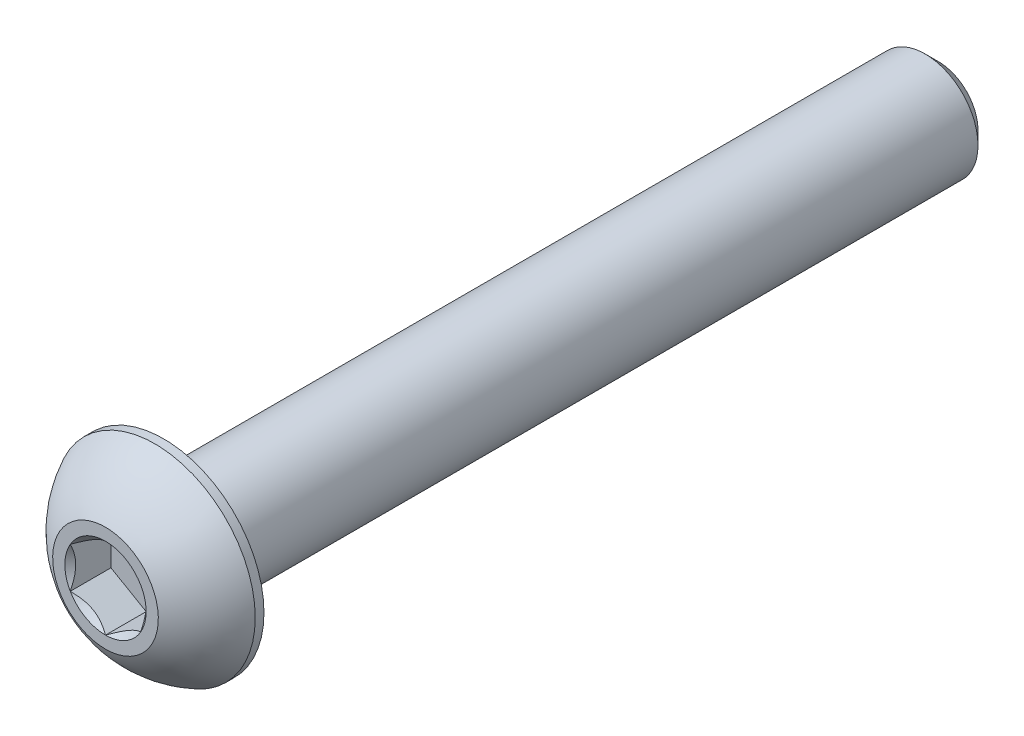
SolidWorks part; units mm, degrees
ref_plane "Front" through (0, 0, 0) normal (0, 0, 1) x (1, 0, 0)
ref_plane "Top" through (0, 0, 0) normal (0, 1, 0) x (1, 0, 0)
ref_plane "Right" through (0, 0, 0) normal (1, 0, 0) x (0, 0, -1)
sketch "Sketch1" plane through (0, 0, 0) normal (1, 0, 0) x (0, 0, -1)
  line L2 (1.65, 1.5) -> (23.65, 1.5)
  line L3 (23.65, 1.5) -> (23.65, 0)
  line L4 (23.65, 0) -> (1.65, 0)
  line L6 (1.4025, 2.85) -> (1.65, 2.85) construction
  line L7 (23.65, 1.5) -> (23.65, -1.5) construction
  line L8 (0, 0) -> (1.65, 0) construction
  line L9 (1.65, 2.85) -> (1.65, -2.85) construction
  line L11 (1.65, 1.5) -> (1.65, 0)
  line L13 (0, 1) -> (0, -1) construction
  line L14 (0, 1) -> (0, 1.5) construction
  arc A3 (0, 1.5) -> (1.4025, 2.85) centre (2.7948, 0) cw construction
  dimension "D1" = 0.2475
revolve "Revolve1" add sketch "Sketch1" angle 360 mid plane about L4
sketch "Sketch3" plane through (0, 0, -23.65) normal (0, 0, -1) x (-1, 0, 0)
  circle A0 centre (0, 0) radius 1.5
curve "Helix/Spiral1" pitch 0.5 height 22.5 turns 45
sketch "Sketch2" plane through (0, 0, 0) normal (1, 0, 0) x (0, 0, -1)
  line L0 (23.65, 1.5) -> (24.0875, 1.5)
  line L1 (24.0875, 1.5) -> (23.9, 1.1752)
  line L2 (23.9, 1.1752) -> (23.8375, 1.1752)
  line L3 (23.8375, 1.1752) -> (23.65, 1.5)
  line L4 (23.7438, 1.3376) -> (23.9938, 1.3376) construction
  dimension "D1" = 60
  dimension "D2" = 0.0625
  dimension "D3" = 0.25
chamfer "Chamfer1" distance 0.375 angle 45 1 edges at (0, 1.5, -23.65)
sweep "Cut-Sweep1" [suppressed] cut profiles "Sketch2" path "Helix/Spiral1"
sketch "Sketch7" plane through (0, 0, 0) normal (1, 0, 0) x (0, 0, -1)
  line L6 (1.4025, 2.85) -> (1.65, 2.85) construction
  line L8 (0, 0) -> (1.65, 0) construction
  line L11 (1.65, 2.85) -> (1.65, -2.85) construction
  line L12 (1.4025, 2.85) -> (1.65, 2.85)
  line L13 (0, 0) -> (1.65, 0)
  line L14 (0, 1) -> (0, -1) construction
  line L15 (1.65, 2.85) -> (1.65, 0)
  line L16 (0, 1.5) -> (0, 0)
  arc A2 (1.4025, 2.85) -> (0, 1.5) centre (2.7948, 0) ccw construction
  arc A3 (1.4025, 2.85) -> (0, 1.5) centre (2.7948, 0) ccw
revolve "Revolve2" add sketch "Sketch7" angle 360 mid plane about L13
sketch "Sketch5" plane through (0, 0, 0) normal (0, 0, 1) x (1, 0, 0)
  line L1 (1, -0.5774) -> (1, 0.5774)
  line L2 (1, 0.5774) -> (0, 1.1547)
  line L3 (0, 1.1547) -> (-1, 0.5774)
  line L4 (-1, 0.5774) -> (-1, -0.5774)
  line L5 (-1, -0.5774) -> (0, -1.1547)
  line L6 (0, -1.1547) -> (1, -0.5774)
  circle A0 centre (0, 0) radius 1 construction
extrude "Cut-Extrude2" cut sketch "Sketch5" against normal blind 1.155
sketch "Sketch6" plane through (0, 0, 0) normal (0, 0, 1) x (1, 0, 0)
  circle A0 centre (0, 0) radius 1.1547
extrude "Cut-Extrude3" cut sketch "Sketch6" against normal blind 1.155 draft 45
sketch "Sketch9" [suppressed] plane through (0, 0, -4.2164) normal (0, 0, 1) x (1, 0, 0)
  circle A2 centre (0, 0) radius 3.9687
extrude "Boss-Extrude2" [suppressed] add sketch "Sketch9" against normal offset from surface (9.525 mm away) 28.575
sketch "Sketch10" plane through (0, 0, 0) normal (1, 0, 0) x (0, 0, -1)
  line L0 (23.65, 1.5) -> (23.65, -1.5) construction
  point P0 (22.9, -1.5)
  dimension "D1" = 0.75
equation "\"D3@Helix/Spiral1\" = \"Lg@Sketch1\" + \"D4@Helix/Spiral1\""
equation "\"D2@Sketch2\" = \"D4@Helix/Spiral1\" * .125"
equation "\"D3@Sketch2\" = \"D4@Helix/Spiral1\" * .5"
equation "\"D1@Chamfer1\" = \"D4@Helix/Spiral1\" * .75"
equation "\"D1@Cut-Extrude2\" = \"Head Ht@Sketch1\" * .7"
equation "\"D1@Sketch1\" = \"Head Ht@Sketch1\" * .15"
equation "\"D1@Sketch10\" = \"D4@Helix/Spiral1\" * 1.5"
equation "\"D1@Cut-Extrude3\" = \"D1@Cut-Extrude2\""
